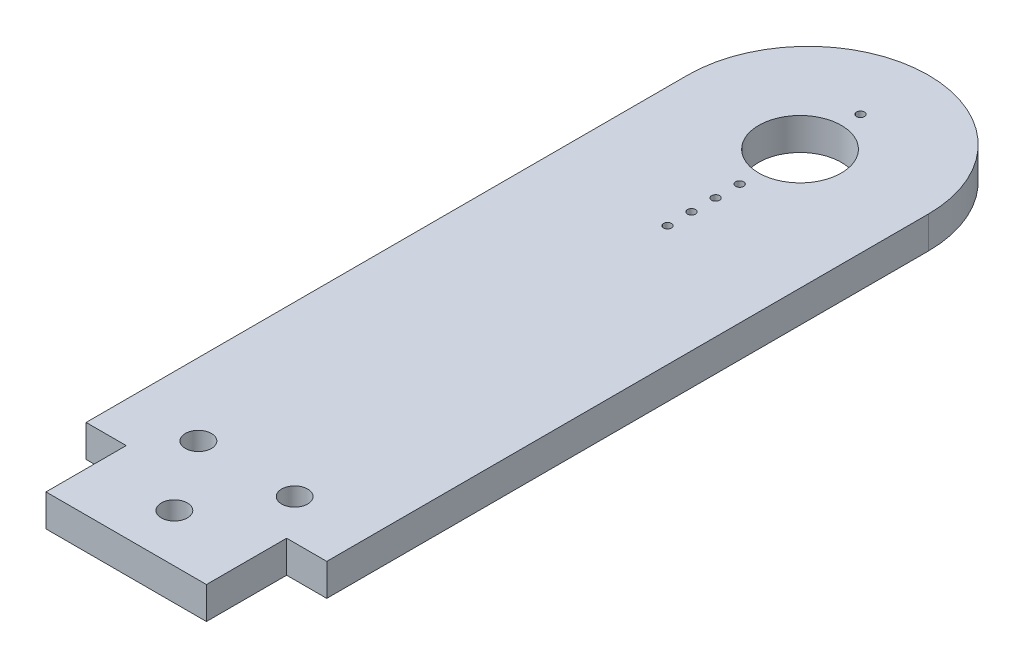
SolidWorks part; units mm, degrees
ref_plane "Спереди" through (0, 0, 0) normal (0, 0, 1) x (1, 0, 0)
ref_plane "Сверху" through (0, 0, 0) normal (0, 1, 0) x (1, 0, 0)
ref_plane "Справа" through (0, 0, 0) normal (1, 0, 0) x (0, 0, -1)
sketch "Эскиз1" plane through (0, 0, 0) normal (0, 1, 0) x (1, 0, 0)
  line L0 (-10, 0) -> (10, 0)
  line L1 (10, 0) -> (10, 10)
  line L2 (10, 10) -> (15, 10)
  line L3 (15, 10) -> (15, 100)
  line L4 (15, 100) -> (-15, 100)
  line L5 (-15, 100) -> (-15, 10)
  line L6 (-15, 10) -> (-10, 10)
  line L7 (-10, 10) -> (-10, 0)
  line L8 (0, 0) -> (0, 100) construction
  line L9 (-15, 15) -> (15, 15) construction
  line L10 (-15, 84) -> (15, 84) construction
  circle A0 centre (-6, 15) radius 1.625
  circle A1 centre (0, 6) radius 1.625
  circle A2 centre (6, 15) radius 1.625
  circle A3 centre (0, 84) radius 5.15
  dimension "D6" = 3.25
  dimension "D10" = 10.3
  dimension "D1" = 20
  dimension "D2" = 10
  dimension "D3" = 5
  dimension "D4" = 90
  dimension "D5" = 5
  dimension "D7" = 9
  dimension "D8" = 6
  dimension "D9" = 84
extrude "Бобышка-Вытянуть1" add sketch "Эскиз1" along normal blind 4
fillet "Скругление1" radius 15 2 edges at (15, 2, -100) (-15, 2, -100)
ref_point "Точка1"
ref_axis "Ось1" through (0, 4, -84) along (1, 0, 0)
sketch "Эскиз3" plane through (0, 4, 0) normal (0, 1, 0) x (1, 0, 0)
  line L0 (0, 100) -> (0, 0) construction
  circle A0 centre (0, 76.47) radius 0.5
  circle A1 centre (0, 73.47) radius 0.5
  circle A2 centre (0, 70.47) radius 0.5
  circle A3 centre (0, 67.47) radius 0.5
  circle A4 centre (0, 91.53) radius 0.5
  point P14 (0, 84)
  dimension "D1" = 1
  dimension "D2" = 7.53
  dimension "D3" = 10.53
  dimension "D4" = 13.53
  dimension "D5" = 16.53
  dimension "D6" = 7.53
extrude "Вырез-Вытянуть1" cut sketch "Эскиз3" against normal through all
